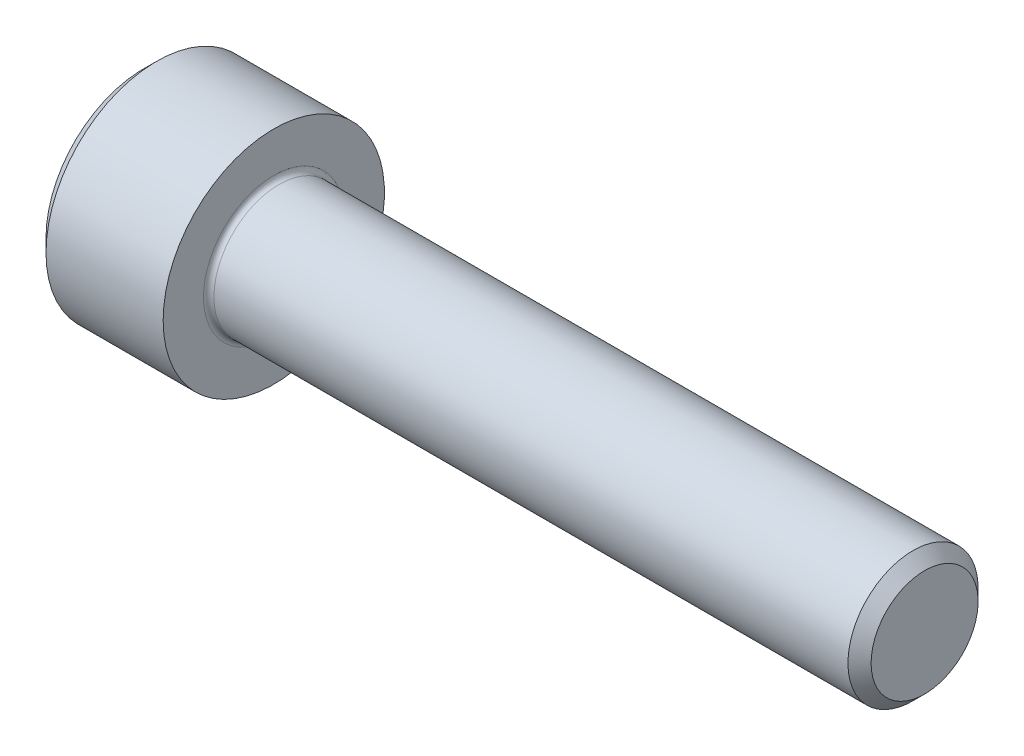
SolidWorks part; units mm, degrees
note: '?' marks a value the reader was unsure of.
revolve "Base-Revolve" add sketch "BodySke"
sketch "BodySke" plane through (0, 0, 0) normal (0, 0, 1) x (1, 0, 0)
  line L0 (0, 0) -> (0, 3.75)
  line L1 (0.5, 4.25) -> (5, 4.25)
  line L2 (5, 4.25) -> (5, 2.5)
  line L3 (5, 2.5) -> (29.555, 2.5)
  line L4 (30, 2.055) -> (30, 0)
  line L5 (30, 0) -> (0, 0)
  line L6 (-31.75, 0) -> (127, 0) construction
  line L7 (0, 3.75) -> (0.5, 4.25)
  line L8 (30, 2.055) -> (29.555, 2.5)
  line L9 (0, -3.75) -> (0.5, -4.25) construction
  line L10 (30, -2.055) -> (29.555, -2.5) construction
  line L11 (5.8, 9.525) -> (5.8, 3.175) construction
  line L12 (22, 9.525) -> (22, 3.175) construction
  line L13 (-20, 9.525) -> (-20, 3.175) construction
  dimension "Diameter" = 5
  dimension "Head_ht" = 5
  dimension "Length" = 25
  dimension "Body_ch_ang" = 45
  dimension "Head_dia" = 8.5
  dimension "Head_ch_ang" = 45
  dimension "Minor_dia" = 4.11
  dimension "Advance" = 0.8
  dimension "Thread_nom" = 8
  dimension "Thread_length" = 50
  dimension "Head_ch_ht" = 0.5
cosmetic thread "ThreadCosmetic" [suppressed]
fillet "Fillet1" radius 0.2 1 edges at (5, 0, 2.5)
ref_plane "Plane1" through (0, 0, 0) normal (0, 0, 1) x (1, 0, 0)
ref_plane "Plane2" through (0, 0, 0) normal (0, 1, 0) x (1, 0, 0)
ref_plane "Plane3" through (0, 0, 0) normal (1, 0, 0) x (0, 0, -1)
sketch "Sketch2" plane through (0, 0, 0) normal (0, 0, 1) x (1, 0, 0)
  line L0 (0, 2.042) -> (2.5, 2.042)
  line L1 (2.5, 2.042) -> (3.6789, 0)
  line L2 (-31.75, 0) -> (127, 0) construction
  line L3 (3.6789, 0) -> (0, 0)
  line L4 (0, 0) -> (0, 2.042)
  line L5 (0, 3.75) -> (0, -3.75) construction
  line L6 (0, 0) -> (47.625, 0) construction
  line L7 (5, -4.25) -> (5, 4.25) construction
  dimension "D1" = 2.042
  dimension "D2" = 60
revolve "Hex-PreBroach" [suppressed] cut sketch "Sketch2" angle 360 about L6
sketch "Sketch3" plane through (0, 0, 0) normal (-1, 0, 0) x (0, 0.5, 0.866)
  line L0 (1.1789, 2.042) -> (-1.1789, 2.042)
  line L1 (-1.1789, 2.042) -> (-2.3579, 0)
  line L2 (1.1789, 2.042) -> (2.3579, 0)
  line L3 (1.1789, -2.042) -> (2.3579, 0)
  line L4 (1.1789, -2.042) -> (-1.1789, -2.042)
  line L5 (-1.1789, -2.042) -> (-2.3579, 0)
  dimension "D1" = 2.042
  dimension "D2" = 2.042
extrude "Hex" [suppressed] cut sketch "Sketch3" against normal blind 2.5
sketch "Sketch4" plane through (0, 0, 0) normal (-1, 0, 0) x (0, 0, 1)
  line L0 (0, 0) -> (2.3876, 0)
  line L1 (0, 0) -> (6.1484, 3.5498) construction
  line L2 (0, 0) -> (1.1938, 2.0677)
  line L3 (1.9883, 0.576) -> (2.2704, 0.7389)
  line L4 (1.493, 1.4339) -> (1.7751, 1.5968)
  arc A0 (1.9883, 0.576) -> (1.493, 1.4339) centre (0, 0) ccw
  arc A1 (2.3876, 0) -> (2.2704, 0.7389) centre (0, 0) ccw
  arc A2 (1.1938, 2.0677) -> (1.7751, 1.5968) centre (0, 0) cw
  dimension "D1" = 30
  dimension "D2" = 60
  dimension "Spline_p_dim" = 0.9906
  dimension "D3" = 0.4953
extrude "Spline" [suppressed] cut sketch "Sketch4" against normal blind 2.5
pattern_circular "CirPattern1" [suppressed] count 0 every? 60?
sketch "Sketch5" plane through (0, 0, 0) normal (0, 0, 1) x (1, 0, 0)
  line L0 (-31.75, 0) -> (127, 0) construction
  line L2 (0, 3.75) -> (0, -3.75) construction
  circle A0 centre (2, 0) radius 0.675
  dimension "Drilled_hole_dia" = 1.35
  dimension "Drilled_hole_loc" = 2
extrude "Hole" [suppressed] cut sketch "Sketch5" against normal through all and the other way through all
pattern_circular "Drilled-4" [suppressed] count 2 every 60
pattern_circular "Drilled-6" [suppressed] count 3 every 60
sketch "ThdSchSke" plane through (0, 0, 0) normal (0, 0, 1) x (1, 0, 0)
  line L0 (5.8, -2.055) -> (5.4884, -2.5)
  line L1 (5.8, -2.055) -> (6.1116, -2.5)
  line L2 (6.1116, -2.5) -> (6.1116, -3.125)
  line L3 (-3.175, 0) -> (5.1513, 0) construction
  line L5 (6.1116, -3.125) -> (5.4884, -3.125)
  line L6 (5.4884, -3.125) -> (5.4884, -2.5)
  line L7 (0, 3.75) -> (0, -3.75) construction
  dimension "Thread_minor" = 4.11
  dimension "Diameter" = 5
  dimension "Start" = 5.8
revolve "ThreadSchematic" [suppressed] cut sketch "ThdSchSke" angle 360 about L3
pattern_linear "ThdSchPat" [suppressed]
equation "\"D2@Sketch3\" = \"Hex_size@Sketch3\" / 2"
equation "\"D1@Sketch3\" = \"Hex_size@Sketch3\" / 2"
equation "\"D1@Sketch2\" = \"Hex_size@Sketch3\" / 2"
equation "\"D3@Sketch4\" = \"Spline_p_dim@Sketch4\" / 2"
equation "\"Thread_minor@ThreadCosmetic\"  =  \"Minor_dia@BodySke\""
equation "\"D2@CirPattern1\" = 360 / \"Num_teeth@CirPattern1\""
equation "\"Wall_thickness@Sketch2\" = \"Head_ht@BodySke\" - \"Key_eng@Hex\""
equation "\"Thread_length@ThreadCosmetic\" = ((sgn( (\"Length@BodySke\" - \"Advance@BodySke\" ) - \"Thread_nom@BodySke\" )-1)*( (\"Length@BodySke\" - \"Advance@BodySke\" ) - \"Thread_nom@BodySke\" ))/-2+ \"Thread_nom@BodySke\""
equation "\"Thread_minor@ThdSchSke\" = \"Minor_dia@BodySke\""
equation "\"Diameter@ThdSchSke\" = \"Diameter@BodySke\""
equation "\"Overcut@ThdSchSke\" = \"Diameter@BodySke\" * 1.25"
equation "\"Start@ThdSchSke\" = \"Head_ht@BodySke\" + \"Length@BodySke\" - \"Thread_length@ThreadCosmetic\"  '---Non-countersunk---"
equation "\"Num_threads@ThdSchPat\" = int( \"Thread_length@ThreadCosmetic\" / \"Advance@BodySke\" + 0.999 )  + 1"
equation "\"Advance@ThdSchPat\" = \"Thread_length@ThreadCosmetic\" /  (\"Num_threads@ThdSchPat\" - 1) 'relax it"
equation "\"Num_threads@ThdSchPat\" = \"Num_threads@ThdSchPat\" - sgn( \"Num_threads@ThdSchPat\" - 1) '---chamfered tips only---"
